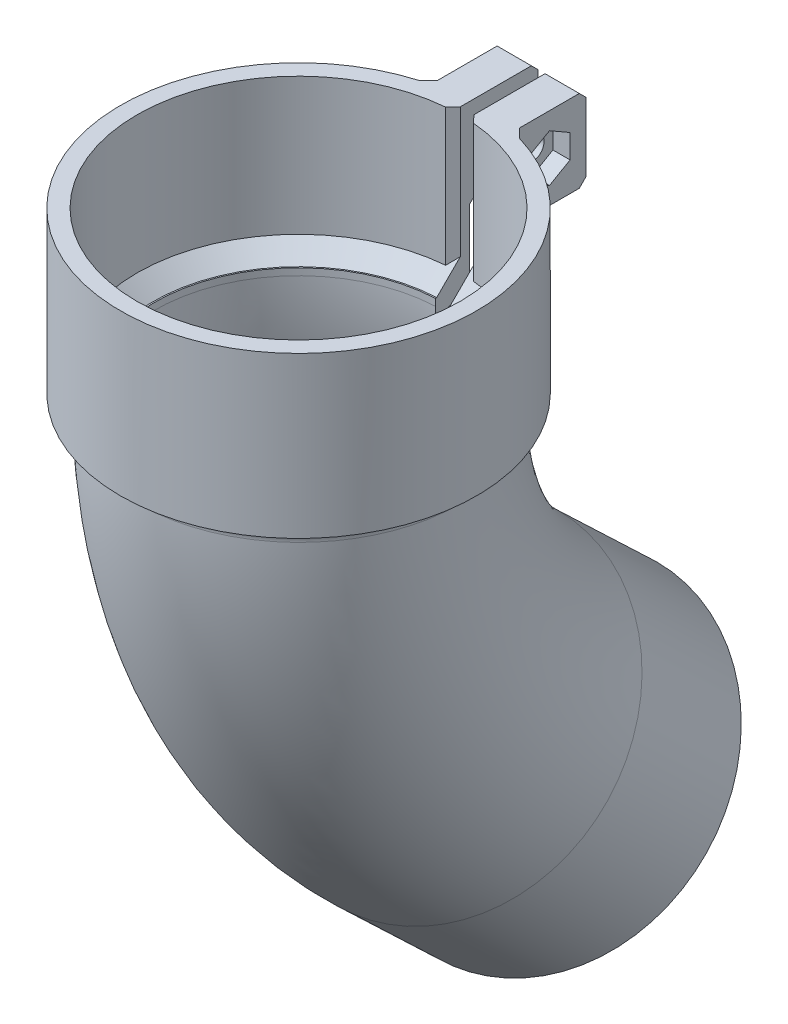
SolidWorks part; units mm, degrees
ref_plane "Front Plane" through (0, 0, 0) normal (0, 0, 1) x (1, 0, 0)
ref_plane "Top Plane" through (0, 0, 0) normal (0, 1, 0) x (1, 0, 0)
ref_plane "Right Plane" through (0, 0, 0) normal (1, 0, 0) x (0, 0, -1)
sketch "Sketch1" plane through (0, 0, 0) normal (1, 0, 0) x (0, 0, -1)
  line L0 (0, 0) -> (0, -70) construction
  line L1 (0, -70) -> (70, -70) construction
  line L3 (0, 0) -> (70, 0) construction
  line L4 (0, 0) -> (37.7271, -31.6568) construction
  line L5 (37.7271, -31.6568) -> (21.7422, -50.7068) construction
  line L6 (21.7422, -50.7068) -> (36.2298, -64.4948)
  arc A0 (0, 0) -> (21.7422, -50.7068) centre (70, 0) ccw
  dimension "D1" = 50
  dimension "D4" = 90
  dimension "D2" = 70
  dimension "D3" = 70
  dimension "D5" = 20
sketch "Sketch2" plane through (0, 0, 0) normal (0, 1, 0) x (1, 0, 0)
  circle A0 centre (0, 0) radius 21
  circle A1 centre (0, 0) radius 23.4
  dimension "D1" = 2.4
  dimension "D2" = 42
sweep "Sweep1" add profiles "Sketch2" path "Sketch1"
sketch "Sketch3" plane through (0, 0, 0) normal (0, 1, 0) x (1, 0, 0)
  circle A0 centre (0, 0) radius 23.6
  circle A1 centre (0, 0) radius 26
  dimension "D1" = 47.2
  dimension "D2" = 52
extrude "Boss-Extrude1" add sketch "Sketch3" along normal blind 23.4 separate body
sketch "Sketch12" plane through (0, 0, 0) normal (0, 1, 0) x (1, 0, 0)
  circle A0 centre (0, 0) radius 21
  circle A1 centre (0, 0) radius 26
extrude "Boss-Extrude3" add sketch "Sketch12" along normal blind 1
fillet "Fillet2" radius 2.4 1 edges at (0, 0, 23.4)
chamfer "Chamfer2" distance 2.4 angle 45 1 edges at (0, 1, 23.6)
ref_plane "Plane1" through (0, 0, -24) normal (0, 0, 1) x (1, 0, 0)
sketch "Sketch13" plane through (0, 0, -24) normal (0, 0, 1) x (1, 0, 0)
  line L0 (0, 0) -> (0, 31.8679) construction
  line L1 (26, 23.4) -> (-26, 23.4) construction
  line L2 (6, 23.4) -> (-6, 23.4)
  line L3 (6, 23.4) -> (6, 11.4)
  line L4 (6, 11.4) -> (-6, 11.4)
  line L5 (-6, 23.4) -> (-6, 11.4)
  line L6 (6, 23.4) -> (-6, 11.4) construction
  line L7 (6, 11.4) -> (-6, 23.4) construction
  point P2 (0, 17.4)
  dimension "D1" = 12
  dimension "D2" = 12
  dimension "D3" = 6
extrude "Boss-Extrude4" add sketch "Sketch13" against normal blind 12
sketch "Sketch18" plane through (6, 0, 0) normal (1, 0, 0) x (0, 0, -1)
  line L0 (25.2982, 23.4) -> (36, 11.4) construction
  circle A0 centre (30.6491, 17.4) radius 1.7
  dimension "D1" = 3.4
extrude "Cut-Extrude4" cut sketch "Sketch18" against normal through all
sketch "Sketch19" plane through (6, 0, 0) normal (1, 0, 0) x (0, 0, -1)
  line L1 (30.6491, 13.9359) -> (33.6491, 15.6679)
  line L2 (33.6491, 15.6679) -> (33.6491, 19.1321)
  line L3 (33.6491, 19.1321) -> (30.6491, 20.8641)
  line L4 (30.6491, 20.8641) -> (27.6491, 19.1321)
  line L5 (27.6491, 19.1321) -> (27.6491, 15.6679)
  line L6 (27.6491, 15.6679) -> (30.6491, 13.9359)
  circle A0 centre (30.6491, 17.4) radius 3 construction
  dimension "D1" = 6
extrude "Cut-Extrude5" cut sketch "Sketch19" against normal blind 2.5
sketch "Sketch20" plane through (0, 0, 0) normal (0, 0, 1) x (1, 0, 0)
  line L0 (0, -2.3399) -> (0, 23.4) construction
  line L1 (6, 23.4) -> (-6, 23.4) construction
  line L3 (1, 23.4) -> (-1, 23.4)
  line L4 (1, 23.4) -> (1, -2.3399)
  line L5 (1, -2.3399) -> (-1, -2.3399)
  line L6 (-1, 23.4) -> (-1, -2.3399)
  line L7 (1, 23.4) -> (-1, -2.3399) construction
  line L8 (1, -2.3399) -> (-1, 23.4) construction
  spline S0 degree 3 poles (1.546, -2.3399) (-0.773, -2.3399) (-1.544, -2.3399) (-3.0819, -2.3402) (-3.8425, -2.3404) (-6.0916, -2.3413) (-7.5513, -2.3421) (-9.6805, -2.3439) (-10.3821, -2.3445) (-11.7347, -2.346) (-12.3892, -2.3468) (-13.6556, -2.3485) (-14.2674, -2.3495) (-15.4481, -2.3516) (-16.0179, -2.3527) (-17.6539, -2.3563) (-18.6199, -2.359) (-19.8889, -2.3636) (-20.2816, -2.3653) (-21.0052, -2.3687) (-21.336, -2.3706) (-22.2132, -2.3763) (-22.6541, -2.3805) (-23.0263, -2.3862) (-23.0918, -2.3874) (-23.2043, -2.3898) (-23.2515, -2.391) (-23.3639, -2.3948) (-23.4005, -2.3974) (-23.3989, -2.4054) (-23.2502, -2.4111) (-22.8748, -2.4188) (-22.79, -2.4204) (-22.6027, -2.4236) (-22.5002, -2.4252) (-22.1666, -2.43) (-21.6523, -2.4366) (-21.0009, -2.4434) (-20.4602, -2.4487) (-20.2712, -2.4504) (-19.8755, -2.4539) (-19.6686, -2.4557) (-18.6005, -2.4646) (-17.633, -2.4717) (-16.0158, -2.4821) (-15.4489, -2.4855) (-14.5555, -2.4906) (-14.2508, -2.4922) (-13.6337, -2.4955) (-13.3205, -2.4971) (-11.7318, -2.5048) (-10.3887, -2.5105) (-8.2645, -2.5176) (-7.5342, -2.5198) (-6.0644, -2.5235) (-5.3231, -2.5251) (-3.0805, -2.5289) (-1.5606, -2.5303) (1.5311, -2.5303) (3.0614, -2.529) (5.3325, -2.5251) (6.0801, -2.5235) (7.543, -2.5197) (8.2605, -2.5176) (9.668, -2.5129) (10.358, -2.5103) (11.7099, -2.5047) (12.375, -2.5017) (14.2894, -2.4923) (15.4663, -2.4856) (17.0855, -2.4752) (17.6007, -2.4717) (18.5802, -2.4645) (19.0369, -2.461) (20.3086, -2.4504) (21.0273, -2.4435) (21.909, -2.4333) (22.1703, -2.43) (22.6152, -2.4235) (22.8005, -2.4204) (23.098, -2.4143) (23.2102, -2.4113) (23.3611, -2.4056) (23.3997, -2.4027) (23.4007, -2.3946) (23.2503, -2.3897) (22.8062, -2.3828) (22.6214, -2.3806) (22.2878, -2.3774) (22.1668, -2.3764) (21.9076, -2.3744) (21.7696, -2.3734) (21.0378, -2.3686) (20.3207, -2.3652) (19.2601, -2.3613) (19.0397, -2.3606) (18.582, -2.3591) (18.3441, -2.3584) (17.612, -2.3563) (17.0982, -2.3551) (15.4814, -2.3515) (14.304, -2.3494) (12.7041, -2.3472) (12.3772, -2.3468) (11.7175, -2.346) (11.3839, -2.3456) (10.3721, -2.3445) (8.9938, -2.3432) (7.5575, -2.3422) (6.0917, -2.3414) (5.3405, -2.341) (3.0743, -2.3402) (1.546, -2.3399) (-0.773, -2.3399) (-1.544, -2.3399) knots -0.03125 -0.03125 0 0 0.015625 0.015625 0.03125 0.03125 0.0625 0.0625 0.078125 0.078125 0.09375 0.09375 0.109375 0.109375 0.125 0.125 0.15625 0.15625 0.171875 0.171875 0.1875 0.1875 0.21875 0.21875 0.226563 0.226563 0.234375 0.234375 0.25 0.25 0.28125 0.28125 0.289063 0.289063 0.296875 0.296875 0.3125 0.328125 0.328125 0.335938 0.335938 0.34375 0.34375 0.375 0.375 0.390625 0.390625 0.398438 0.398438 0.40625 0.40625 0.4375 0.4375 0.453125 0.453125 0.46875 0.46875 0.5 0.5 0.53125 0.53125 0.546875 0.546875 0.5625 0.5625 0.578125 0.578125 0.59375 0.59375 0.625 0.625 0.640625 0.640625 0.65625 0.65625 0.6875 0.6875 0.703125 0.703125 0.71875 0.71875 0.734375 0.734375 0.75 0.75 0.78125 0.78125 0.796875 0.796875 0.804688 0.804688 0.8125 0.8125 0.84375 0.84375 0.851563 0.851563 0.859375 0.859375 0.875 0.875 0.90625 0.90625 0.914063 0.914063 0.921875 0.921875 0.9375 0.953125 0.953125 0.96875 0.96875 1 1 1.015625 1.015625 1.03125 only from (0, -2.3399) to (0, -2.3399) construction
  point P6 (0, 10.5301)
  dimension "D1" = 2
  dimension "D2" = 25.7399
extrude "Cut-Extrude6" cut sketch "Sketch20" against normal through all
chamfer "Chamfer3" distance 1 angle 45 10 edges at (-1, 13.4, -23.5788) (1, 13.4, -23.5788) (-3.5166, 11.4, -25.7611) (3.5166, 11.4, -25.7611) (6, 17.4, -25.2982) (-6, 17.4, -25.2982) (-3.5, 23.4, -36) (-3.5, 11.4, -36) (3.5, 11.4, -36) (3.5, 23.4, -36)
sketch "Sketch22" plane through (-6, 0, 0) normal (-1, 0, 0) x (0, 0, 1)
  circle A0 centre (-30.6491, 17.4) radius 3
  dimension "D1" = 6
extrude "Cut-Extrude7" cut sketch "Sketch22" against normal blind 2.5
